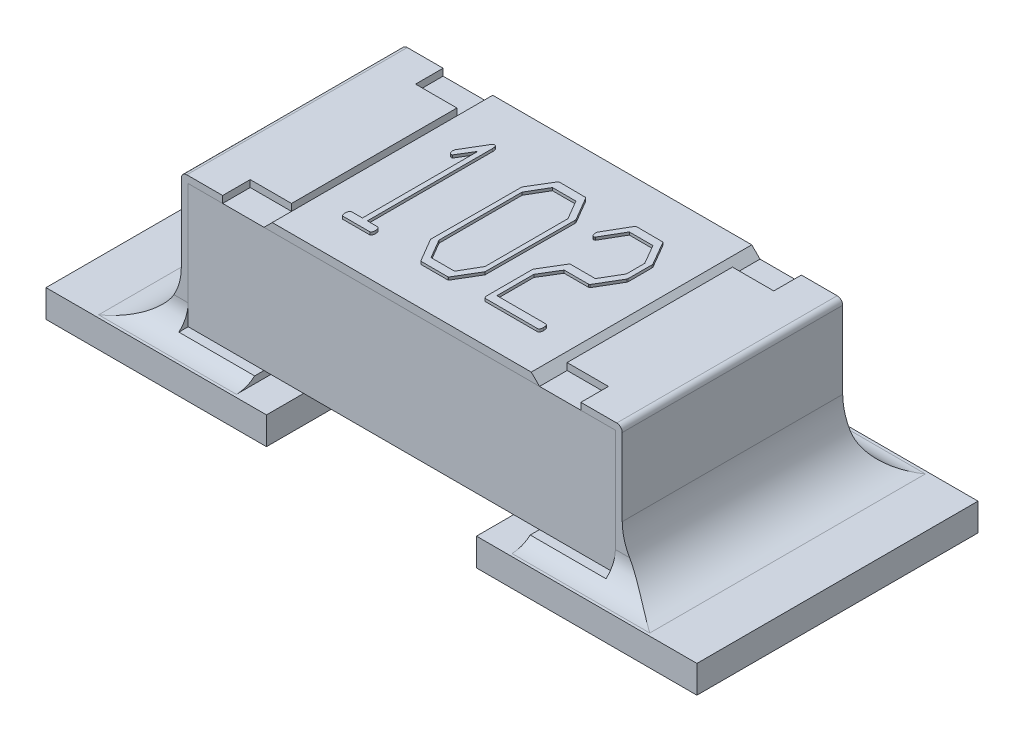
SolidWorks part; units mm, degrees
material "Ceramic Porcelain"
ref_plane "Front Plane" through (0, 0, 0) normal (0, 0, 1) x (1, 0, 0)
ref_plane "Top Plane" through (0, 0, 0) normal (0, 1, 0) x (1, 0, 0)
ref_plane "Right Plane" through (0, 0, 0) normal (1, 0, 0) x (0, 0, -1)
sketch "Sketch1" plane through (0, 0, 0) normal (1, 0, 0) x (0, 0, -1)
  line L0 (0, 55) -> (0, -55) construction
  line L1 (-0.4, 0.575) -> (0.4, 0.575)
  line L2 (-0.4, 0.575) -> (-0.4, 0.125)
  line L3 (-0.4, 0.125) -> (0.4, 0.125)
  line L4 (0.4, 0.575) -> (0.4, 0.125)
  line L5 (55, 0) -> (-55, 0) construction
  dimension "D1" = 0.8
  dimension "D2" = 0.4
  dimension "D3" = 0.45
  dimension "D4" = 0.125
extrude "Boss-Extrude1" add sketch "Sketch1" along normal mid plane 1.55
sketch "Sketch2" plane through (0, 0, 0) normal (0, 0, 1) x (1, 0, 0)
  line L0 (-0.5, 0.6) -> (-0.78, 0.6)
  line L1 (-0.8, 0.58) -> (-0.8, 0.1)
  line L2 (-0.8, 0.1) -> (-0.5, 0.1)
  line L3 (-0.5, 0.1) -> (-0.5, 0.125)
  line L4 (0.775, 0.125) -> (-0.775, 0.125) construction
  line L5 (-0.5, 0.125) -> (-0.775, 0.125)
  line L6 (-0.775, 0.125) -> (-0.775, 0.575)
  line L7 (-0.775, 0.575) -> (-0.5, 0.575)
  line L8 (0.775, 0.575) -> (-0.775, 0.575) construction
  line L9 (-0.5, 0.575) -> (-0.5, 0.6)
  line L11 (0.5, 0.575) -> (0.5, 0.6)
  line L12 (0.5, 0.6) -> (0.78, 0.6)
  line L13 (0.8, 0.58) -> (0.8, 0.1)
  line L14 (0.8, 0.1) -> (0.5, 0.1)
  line L15 (0.5, 0.1) -> (0.5, 0.125)
  line L16 (0.5, 0.125) -> (0.775, 0.125)
  line L17 (0.775, 0.125) -> (0.775, 0.575)
  line L18 (0.775, 0.575) -> (0.5, 0.575)
  arc A0 (0.78, 0.6) -> (0.8, 0.58) centre (0.78, 0.58) cw
  arc A1 (-0.78, 0.6) -> (-0.8, 0.58) centre (-0.78, 0.58) ccw
  point P28 (-0.8, 0.6)
  dimension "D6" = 0.02
  dimension "D1" = 0.025
  dimension "D2" = 0.025
  dimension "D3" = 0.025
  dimension "D4" = 0.3
  dimension "D5" = 0.3
extrude "Boss-Extrude2" add sketch "Sketch2" along normal mid plane 0.8 separate body
sketch "Sketch3" plane through (0, 0.6, 0) normal (0, 1, 0) x (1, 0, 0)
  line L0 (0.5, -0.4) -> (0.5, 0.4) construction
  line L1 (-0.5, 0.4) -> (-0.65, 0.4)
  line L2 (-0.5, 0.4) -> (-0.5, 0.3)
  line L3 (-0.5, 0.3) -> (-0.65, 0.3)
  line L4 (-0.65, 0.4) -> (-0.65, 0.3)
  line L5 (-0.5, -0.4) -> (-0.65, -0.4)
  line L6 (-0.5, -0.4) -> (-0.5, -0.3)
  line L7 (-0.5, -0.3) -> (-0.65, -0.3)
  line L8 (-0.65, -0.4) -> (-0.65, -0.3)
  line L9 (0.5, -0.4) -> (0.65, -0.4)
  line L10 (0.5, -0.4) -> (0.5, -0.3)
  line L11 (0.5, -0.3) -> (0.65, -0.3)
  line L12 (0.65, -0.4) -> (0.65, -0.3)
  line L13 (0.775, -0.4) -> (-0.775, -0.4) construction
  line L15 (0.5, 0.4) -> (0.65, 0.4)
  line L16 (0.5, 0.4) -> (0.5, 0.3)
  line L17 (0.5, 0.3) -> (0.65, 0.3)
  line L18 (0.65, 0.4) -> (0.65, 0.3)
  dimension "D1" = 0.15
  dimension "D2" = 0.1
extrude "Cut-Extrude1" cut sketch "Sketch3" against normal blind 0.025
sketch "Sketch4" plane through (0, 0, 0) normal (0, 0, 1) x (1, 0, 0)
  line L0 (-0.5, 0.575) -> (0.5, 0.575)
  line L1 (0.5, 0.575) -> (0.47, 0.605)
  line L2 (0.47, 0.605) -> (-0.47, 0.605)
  line L3 (-0.47, 0.605) -> (-0.5, 0.575)
  dimension "D1" = 45
  dimension "D2" = 45
  dimension "D3" = 0.03
extrude "Boss-Extrude3" add sketch "Sketch4" along normal mid plane 0.8 separate body
sketch "Sketch6" plane through (0, 0.605, 0) normal (0, 1, 0) x (1, 0, 0)
  line L0 (-0.4, -0.25) -> (0.4, -0.25) construction
  line L1 (0, -0.2777) -> (0, 0.2777) construction
  line L2 (-0.2777, 0) -> (0.2777, 0) construction
  text T0 "102\r\n" font "SWMono" height 0.5
  dimension "D1" = 0.8
  dimension "D2" = 0.4
  dimension "D3" = 0.25
extrude "Boss-Extrude4" add sketch "Sketch6" along normal blind 0.01
sketch "Sketch7" plane through (0, 0, 0) normal (0, 1, 0) x (1, 0, 0)
  line L0 (0, -0.2833) -> (0, 0.2833) construction
  line L1 (-0.381, -0.51) -> (-1.181, -0.51)
  line L2 (-0.381, -0.51) -> (-0.381, 0.51)
  line L3 (-0.381, 0.51) -> (-1.181, 0.51)
  line L4 (-1.181, -0.51) -> (-1.181, 0.51)
  line L5 (0.381, -0.51) -> (1.181, -0.51)
  line L6 (0.381, -0.51) -> (0.381, 0.51)
  line L7 (0.381, 0.51) -> (1.181, 0.51)
  line L8 (1.181, -0.51) -> (1.181, 0.51)
  line L9 (-0.2833, 0) -> (0.2833, 0) construction
  dimension "D1" = 0.8
  dimension "D2" = 0.381
  dimension "D3" = 0.381
  dimension "D4" = 1.02
  dimension "D5" = 0.51
extrude "Boss-Extrude5" add sketch "Sketch7" along normal blind 0.1
fillet "Fillet3" radius 0.2 1 edges at (-0.8, 0.1, 0)
fillet "Fillet4" radius 0.2 1 edges at (0.8, 0.1, 0)
fillet "Fillet5" radius 0.1 2 edges at (0.75, 0.1, -0.4) (0.75, 0.1, 0.4)
fillet "Fillet6" radius 0.1 2 edges at (-0.75, 0.1, 0.4) (-0.75, 0.1, -0.4)
